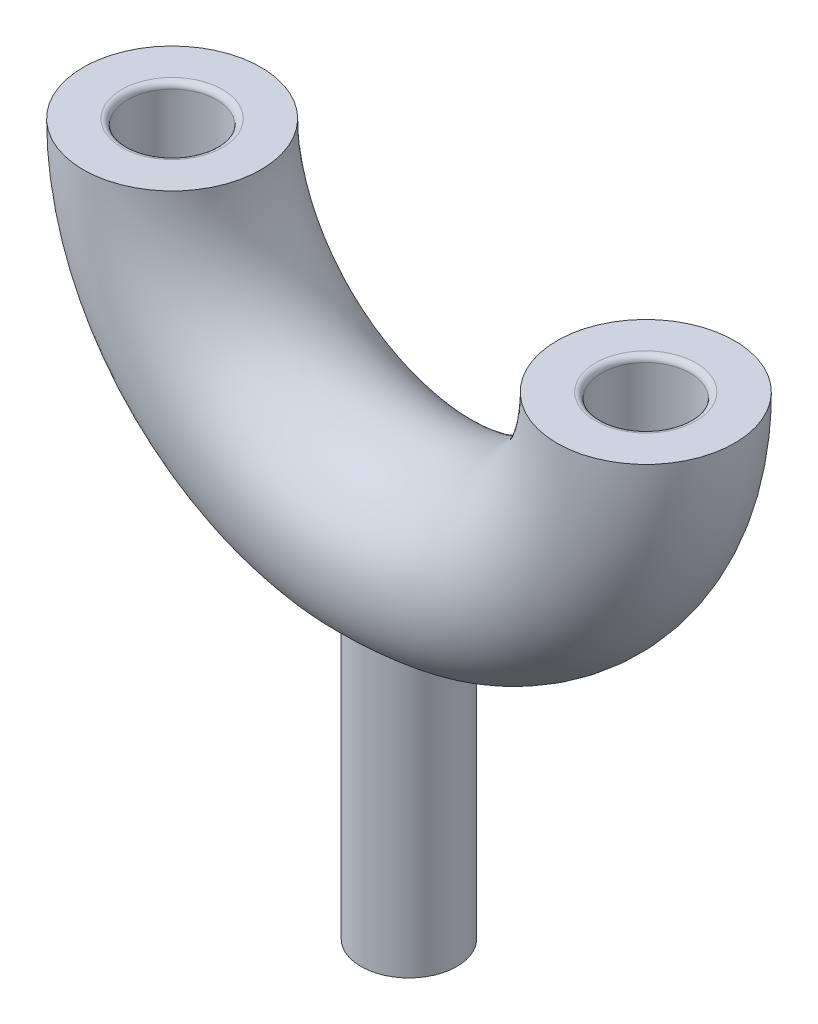
SolidWorks part; units mm, degrees
ref_plane "Front Plane" through (0, 0, 0) normal (0, 0, 1) x (1, 0, 0)
ref_plane "Top Plane" through (0, 0, 0) normal (0, 1, 0) x (1, 0, 0)
ref_plane "Right Plane" through (0, 0, 0) normal (1, 0, 0) x (0, 0, -1)
sketch "Sketch2" plane through (0, 0, 0) normal (0, 1, 0) x (1, 0, 0)
  circle A0 centre (0, 0) radius 10.287
  dimension "D1" = 20.574
extrude "Boss-Extrude1" add sketch "Sketch2" along normal blind 76.2
sketch "Sketch3" plane through (0, 0, 0) normal (0, 0, 1) x (1, 0, 0)
  line L0 (10.287, 76.2) -> (-10.287, 76.2) construction
  circle A0 centre (0, 127) radius 50.8
  dimension "D1" = 101.6
  dimension "D2" = 50.8
sweep "Sweep1" add path "Sketch3" circular profile diameter 38.1 parameters "D3"=38.1
sketch "Sketch10" plane through (0, 0, 0) normal (0, 1, 0) x (1, 0, 0)
  line L1 (-74.079, 24.7388) -> (74.079, 24.7388)
  line L2 (-74.079, 24.7388) -> (-74.079, -24.7388)
  line L3 (-74.079, -24.7388) -> (74.079, -24.7388)
  line L4 (74.079, 24.7388) -> (74.079, -24.7388)
  line L5 (-74.079, 24.7388) -> (74.079, -24.7388) construction
  line L6 (-74.079, -24.7388) -> (74.079, 24.7388) construction
  circle A0 centre (0, 0) radius 10.287
  point P0 (0, 0)
extrude "Cut-Extrude1" cut sketch "Sketch10" along normal blind 63.5
fillet "Fillet1" radius 2.54 1 edges at (-7.8588, 63.5, 13.7504)
sketch "Sketch11" plane through (0, 0, 0) normal (0, 0, 1) x (1, 0, 0)
  line L0 (94.8943, 127) -> (-89.637, 127) construction
  line L1 (94.8943, 127) -> (-89.637, 127)
  line L2 (-89.637, 127) -> (-89.637, 212.5248)
  line L3 (-89.637, 212.5248) -> (94.8943, 212.5248)
  line L4 (94.8943, 212.5248) -> (94.8943, 127)
extrude "Cut-Extrude2" cut sketch "Sketch11" against normal blind 63.5 and the other way blind 63.5
sketch "Sketch12" plane through (0, 127, 0) normal (0, 1, 0) x (1, 0, 0)
  line L0 (80.2241, 0) -> (-88.1035, 0) construction
  line L1 (50.8, 19.05) -> (50.8, -19.05) construction
  line L2 (-50.8, 19.05) -> (-50.8, -19.05) construction
  circle A0 centre (50.8, 0) radius 19.05 construction
  circle A1 centre (50.8, 0) radius 9.525
  circle A2 centre (-50.8, 0) radius 9.525
  dimension "D1" = 19.05
  dimension "D2" = 19.05
extrude "Cut-Extrude3" cut sketch "Sketch12" against normal blind 19.05
fillet "Fillet2" radius 1.27 2 edges at (50.8, 127, 9.525) (-50.8, 127, 9.525)
